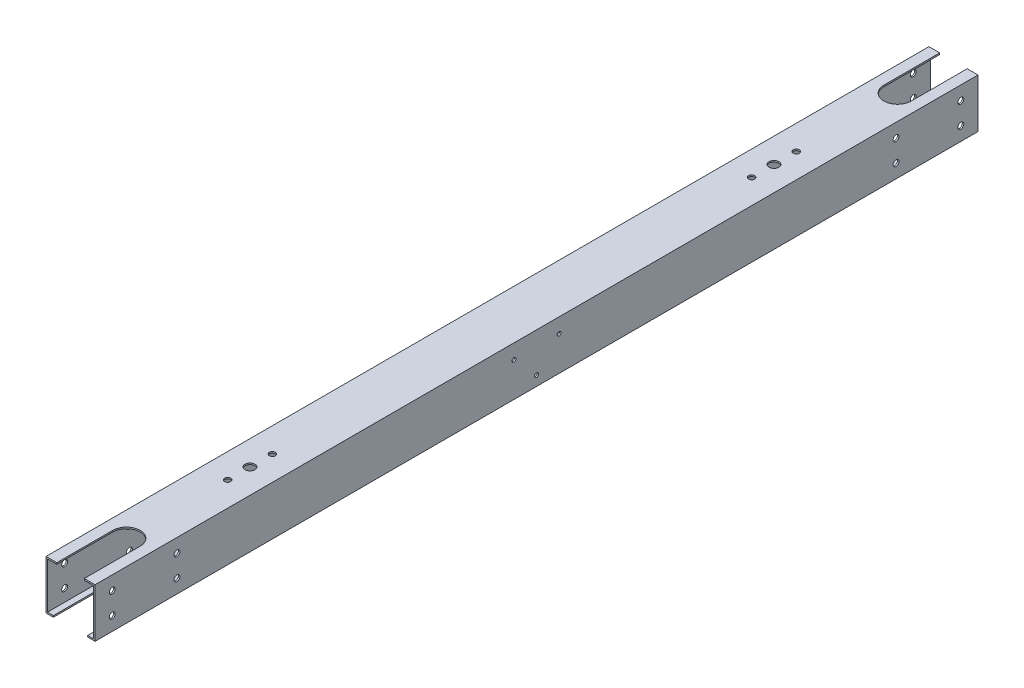
SolidWorks part; units mm, degrees
material "6061 Alloy"
ref_plane "Front Plane" through (0, 0, 0) normal (0, 0, 1) x (1, 0, 0)
ref_plane "Top Plane" through (0, 0, 0) normal (0, 1, 0) x (1, 0, 0)
ref_plane "Right Plane" through (0, 0, 0) normal (1, 0, 0) x (0, 0, -1)
sketch "Sketch1" plane through (0, 0, 0) normal (0, 0, 1) x (1, 0, 0)
  line L1 (-23.5, 23.5) -> (23.5, 23.5)
  line L2 (-23.5, 23.5) -> (-23.5, -23.5)
  line L3 (-23.5, -23.5) -> (23.5, -23.5)
  line L4 (23.5, 23.5) -> (23.5, -23.5)
  line L5 (-23.5, 23.5) -> (23.5, -23.5) construction
  line L6 (-23.5, -23.5) -> (23.5, 23.5) construction
  line L7 (-25, 25) -> (25, 25)
  line L8 (-25, 25) -> (-25, -25)
  line L9 (-25, -25) -> (25, -25)
  line L10 (25, 25) -> (25, -25)
  line L11 (-25, 25) -> (25, -25) construction
  line L12 (-25, -25) -> (25, 25) construction
  point P0 (0, 0)
  point P6 (0, 0)
  dimension "D1" = 50
  dimension "D2" = 47
  dimension "D3" = 50
  dimension "D4" = 47
extrude "Boss-Extrude1" add sketch "Sketch1" along normal blind 900
sketch "Sketch2" plane through (25, 0, 0) normal (1, 0, 0) x (0, 0, -1)
  line L0 (-900, -25) -> (0, -25) construction
  line L1 (-450, -25) -> (-450, 25) construction
  line L2 (-900, 25) -> (0, 25) construction
  line L3 (0, -25) -> (0, 25) construction
  circle A0 centre (-450, -15) radius 2
  circle A1 centre (-427, 10) radius 2
  circle A2 centre (-473, 10) radius 2
  point P0 (-450, -25)
  dimension "D4" = 4
  dimension "D1" = 10
  dimension "D2" = 25
  dimension "D3" = 23
  dimension "D5" = 450
extrude "Cut-Extrude1" cut sketch "Sketch2" against normal blind 59
sketch "Sketch3" plane through (0, 25, 0) normal (0, 1, 0) x (1, 0, 0)
  line L0 (0, -843) -> (0, -913.9861) construction
  line L5 (14, -843) -> (14, -913.9861)
  line L6 (-14, -843) -> (-14, -913.9861)
  line L7 (25, -900) -> (-25, -900) construction
  arc A0 (14, -843) -> (-14, -843) centre (0, -843) ccw
  arc A1 (-14, -913.9861) -> (14, -913.9861) centre (0, -913.9861) ccw
  point P2 (0, -878.4931)
  dimension "D2" = 14
  dimension "D1" = 57
extrude "Cut-Extrude2" cut sketch "Sketch3" against normal blind 10
sketch "Sketch4" plane through (0, -25, 0) normal (0, -1, 0) x (1, 0, 0)
  line L0 (0.0011, 850) -> (0.0011, 939.0785) construction
  line L1 (-17.4989, 850) -> (-17.4989, 939.0785)
  line L2 (17.5011, 850) -> (17.5011, 939.0785)
  line L3 (25, 900) -> (25, 0) construction
  line L4 (-25, 900) -> (25, 900) construction
  arc A0 (-17.4989, 850) -> (17.5011, 850) centre (0.0011, 850) ccw
  arc A1 (17.5011, 939.0785) -> (-17.4989, 939.0785) centre (0.0011, 939.0785) ccw
  point P2 (0.0011, 894.5393)
  dimension "D2" = 17.5
  dimension "D1" = 50
extrude "Cut-Extrude3" cut sketch "Sketch4" against normal blind 10
sketch "Sketch5" plane through (25, 0, 0) normal (1, 0, 0) x (0, 0, -1)
  line L0 (-900, -25) -> (0, -25) construction
  line L1 (-900, 25) -> (0, 25) construction
  line L2 (-900, -25) -> (-900, 25) construction
  line L3 (-849.5, 25) -> (-849.5, -25) construction
  circle A0 centre (-882.5, 11) radius 3
  circle A2 centre (-882.5, -11) radius 3
  circle A3 centre (-816.5, -11) radius 3
  circle A4 centre (-816.5, 11) radius 3
  dimension "D4" = 6
  dimension "D6" = 6
  dimension "D1" = 33
  dimension "D2" = 14
  dimension "D3" = 14
  dimension "D7" = 17.5
extrude "Cut-Extrude4" cut sketch "Sketch5" against normal blind 55
ref_plane "Plane1" through (0, 0, 450) normal (0, 0, 1) x (1, 0, 0)
mirror "Mirror1" about plane through (0, 0, 450) normal (0, 0, 1) of "Cut-Extrude4", "Cut-Extrude3", "Cut-Extrude2"
sketch "Sketch6" plane through (0, 25, 0) normal (0, 1, 0) x (1, 0, 0)
  line L0 (0, -694.2275) -> (0, -739.8525) construction
  line L2 (-27.5, -450) -> (27.5, -450) construction
  circle A0 centre (0, -694.2275) radius 3.125
  circle A1 centre (0, -739.8525) radius 3.125
  circle A2 centre (0, -717.04) radius 5
  point P8 (0, -717.04)
  dimension "D1" = 6.25
  dimension "D2" = 6.25
  dimension "D5" = 10
  dimension "D3" = 45.625
  dimension "D4" = 267.04
extrude "Cut-Extrude5" cut sketch "Sketch6" against normal blind 10
mirror "Mirror2" about plane through (0, 0, 450) normal (0, 0, 1) of "Cut-Extrude5"
